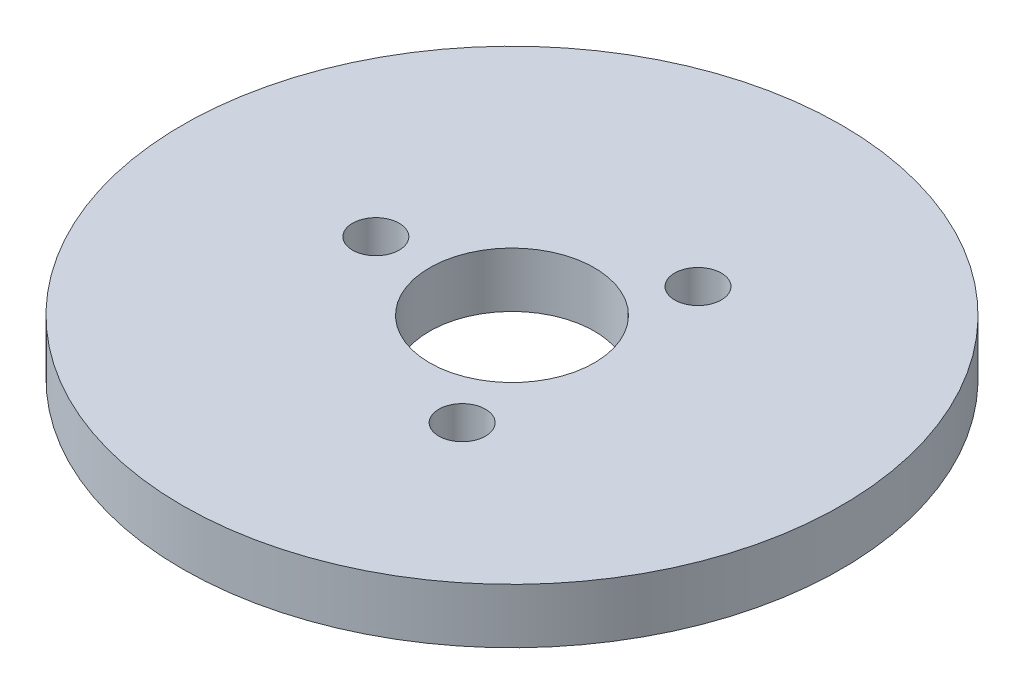
SolidWorks part; units mm, degrees
ref_plane "Front Plane" through (0, 0, 0) normal (0, 0, 1) x (1, 0, 0)
ref_plane "Top Plane" through (0, 0, 0) normal (0, 1, 0) x (1, 0, 0)
ref_plane "Right Plane" through (0, 0, 0) normal (1, 0, 0) x (0, 0, -1)
sketch "Sketch1" plane through (0, 0, 0) normal (0, 1, 0) x (1, 0, 0)
  circle A0 centre (0, 0) radius 90
  dimension "FLANGE_OD" = 180
extrude "Boss-Extrude1" add sketch "Sketch1" along normal blind 15
sketch "Sketch2" plane through (0, 0, 0) normal (0, 1, 0) x (1, 0, 0)
  circle A0 centre (0, 0) radius 22.5
  dimension "BORE_D" = 45
extrude "Cut-Extrude1" cut sketch "Sketch2" along normal through all
sketch "Sketch3" plane through (0, 15, 0) normal (0, 1, 0) x (1, 0, 0)
  circle A0 centre (0, 0) radius 37.1814 construction
  circle A1 centre (-37.1814, 0) radius 6.3769
  dimension "BOLT_D" = 12.7537
  dimension "BOLT_PCD" = 74.3628
extrude "Cut-Extrude2" cut sketch "Sketch3" against normal blind 14.4478
pattern_circular "CirPattern1" count 3 over 360 about axis through (0, 0, 0) along (0, 1, 0) of "Cut-Extrude2"
